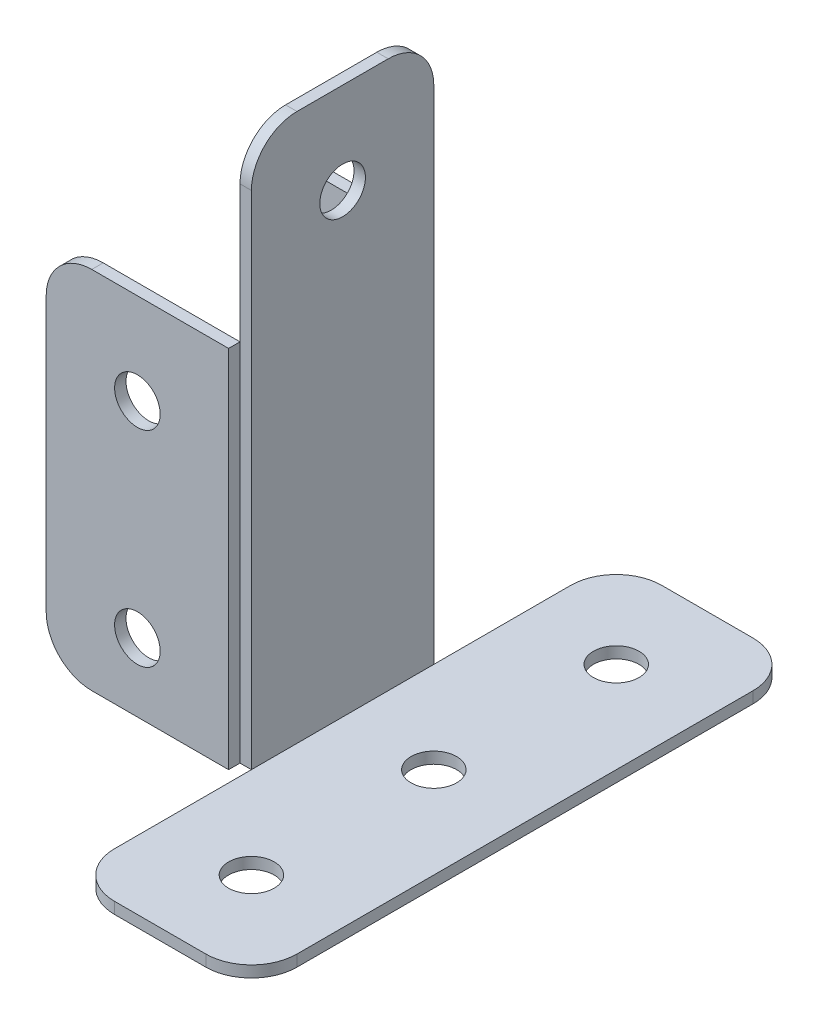
SolidWorks part; units mm, degrees
ref_plane "Front Plane" through (0, 0, 0) normal (0, 0, 1) x (1, 0, 0)
ref_plane "Top Plane" through (0, 0, 0) normal (0, 1, 0) x (1, 0, 0)
ref_plane "Right Plane" through (0, 0, 0) normal (1, 0, 0) x (0, 0, -1)
sketch "Sketch1" plane through (0, 0, 0) normal (0, 0, 1) x (1, 0, 0)
  line L0 (0, 0) -> (-25.4, 0)
  line L1 (-25.4, 0) -> (-25.4, 50.8)
  line L2 (-25.4, 50.8) -> (0, 50.8)
  line L3 (0, 50.8) -> (0, 0)
  line L4 (-12.7, 50.8) -> (-12.7, 0) construction
  circle A0 centre (-12.7, 38.1) radius 3.175
  circle A1 centre (-12.7, 9.525) radius 3.175
  dimension "D5" = 6.35
  dimension "D1" = 12.7
  dimension "D2" = 28.575
  dimension "D3" = 9.525
  dimension "D4" = 25.4
extrude "Boss-Extrude1" add sketch "Sketch1" along normal blind 1.5875
extrude "Boss-Extrude2" add sketch "Sketch1<2>" against normal blind 1.5875 from offset 25.4 separate body offset against normal yes
sketch "Sketch1<2>" plane through (0, 0, 0) normal (0, 0, 1) x (1, 0, 0) same geometry as "Sketch1"
sketch "Sketch3" plane through (0, 0, 0) normal (1, 0, 0) x (0, 0, -1)
  line L0 (25.4, 76.2) -> (0, 50.8) construction
  line L1 (25.4, 50.8) -> (0, 50.8) construction
  line L2 (25.4, 50.8) -> (25.4, 0)
  line L3 (25.4, 0) -> (0, 0)
  line L4 (0, 50.8) -> (0, 0)
  line L5 (25.4, 50.8) -> (0, 50.8) construction
  line L6 (25.4, 50.8) -> (25.4, 76.2)
  line L7 (25.4, 76.2) -> (0, 76.2)
  line L8 (0, 50.8) -> (0, 76.2)
  circle A0 centre (12.7, 63.5) radius 3.175
  dimension "D2" = 6.35
  dimension "D1" = 25.4
extrude "Boss-Extrude3" add sketch "Sketch3" along normal blind 1.5875 separate body
sketch "Sketch4" plane through (0, 0, 0) normal (0, 1, 0) x (1, 0, 0)
  line L1 (1.5875, -50.8) -> (26.9875, -50.8) construction
  line L3 (26.9875, 50.8) -> (1.5875, 50.8)
  line L4 (1.5875, 50.8) -> (1.5875, 25.4)
  line L5 (1.5875, 25.4) -> (1.5875, 0)
  line L6 (1.5875, 25.4) -> (26.9875, 25.4)
  line L7 (26.9875, 50.8) -> (26.9875, 25.4)
  line L8 (1.5875, -25.4) -> (26.9875, -25.4)
  line L9 (14.2875, -50.8) -> (14.2875, 50.8) construction
  line L10 (26.9875, -25.4) -> (26.9875, -50.8) construction
  line L11 (1.5875, 0) -> (1.5875, -25.4)
  line L12 (1.5875, -50.8) -> (1.5875, -25.4) construction
  line L13 (26.9875, -25.4) -> (26.9875, 25.4)
  circle A0 centre (14.2875, 12.7) radius 3.175
  circle A1 centre (14.2875, -12.7) radius 3.175
  circle A2 centre (14.2875, -38.1) radius 3.175 construction
  circle A3 centre (14.2875, 38.1) radius 3.175
  dimension "D2" = 6.35
  dimension "D1" = 12.7
  dimension "D3" = 12.7
  dimension "D4" = 25.4
  dimension "D5" = 12.7
  dimension "D6" = 12.7
  dimension "D7" = 12.7
  dimension "D8" = 12.7
  dimension "D9" = 25.4
extrude "Boss-Extrude4" add sketch "Sketch4" against normal blind 1.5875 separate body contours L8 L13 L6 L5 L11 A1 A0 | L7 L3 L4 L6 A3 region at (26.6283, 0, -38.1) region at (14.2875, 0, 0)
fillet "Fillet1" radius 6.35 4 edges at (1.5875, -0.7937, -50.8) (26.9875, -0.7937, -50.8) (26.9875, -0.7937, 25.4) (1.5875, -0.7937, 25.4)
fillet "Fillet2" radius 6.35 2 edges at (-25.4, 0, -26.1937) (-25.4, 50.8, -26.1937)
fillet "Fillet3" radius 6.35 2 edges at (-25.4, 50.8, 0.7937) (-25.4, 0, 0.7937)
fillet "Fillet4" radius 6.35 2 edges at (0.7937, 76.2, -25.4) (0.7937, 76.2, 0)
